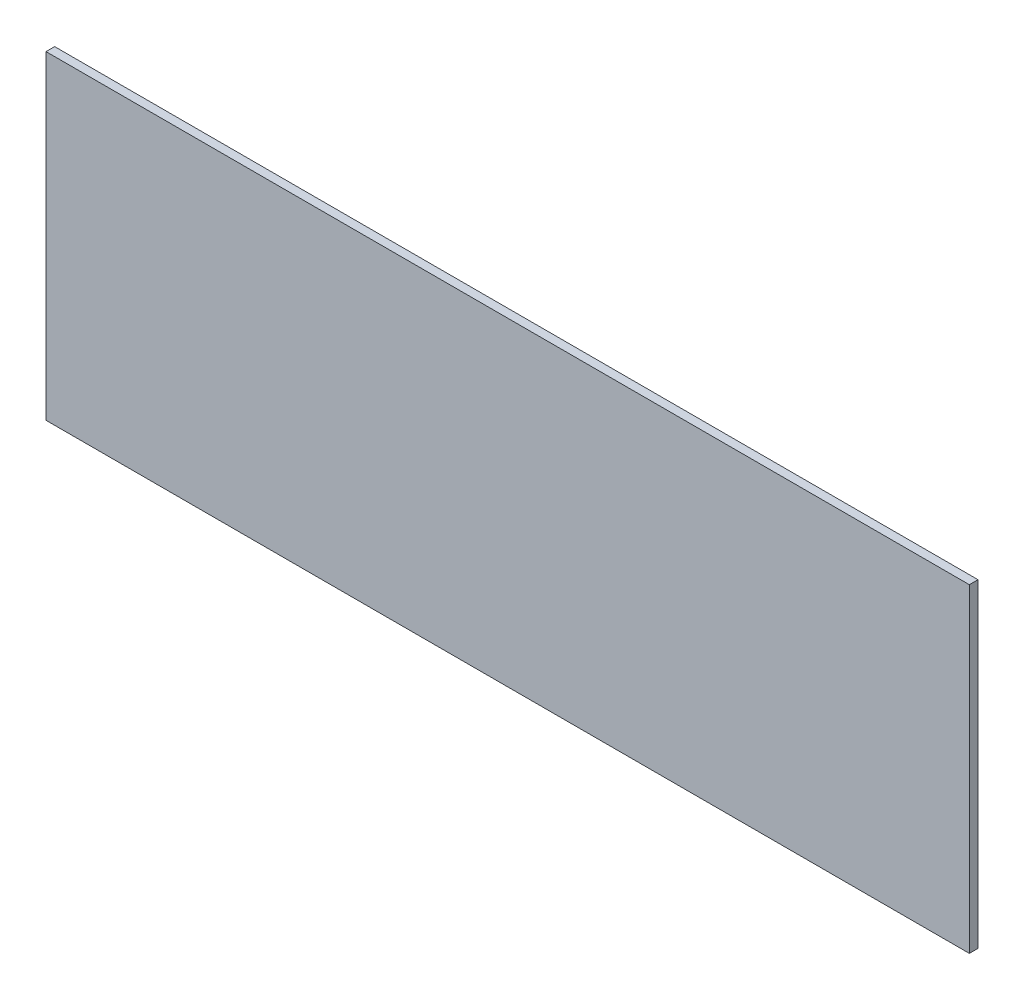
SolidWorks part; units mm, degrees
material "Custom Plastic"
ref_plane "Front Plane" through (0, 0, 0) normal (0, 0, 1) x (1, 0, 0)
ref_plane "Top Plane" through (0, 0, 0) normal (0, 1, 0) x (1, 0, 0)
ref_plane "Right Plane" through (0, 0, 0) normal (1, 0, 0) x (0, 0, -1)
sketch "Sketch1" plane through (0, 0, 0) normal (0, 0, 1) x (1, 0, 0)
  line L1 (-480, -166) -> (480, -166)
  line L2 (-480, -166) -> (-480, 166)
  line L3 (-480, 166) -> (480, 166)
  line L4 (480, -166) -> (480, 166)
  line L5 (-480, -166) -> (480, 166) construction
  line L6 (-480, 166) -> (480, -166) construction
  point P0 (0, 0)
extrude "Boss-Extrude1" add sketch "Sketch1" along normal blind 9
